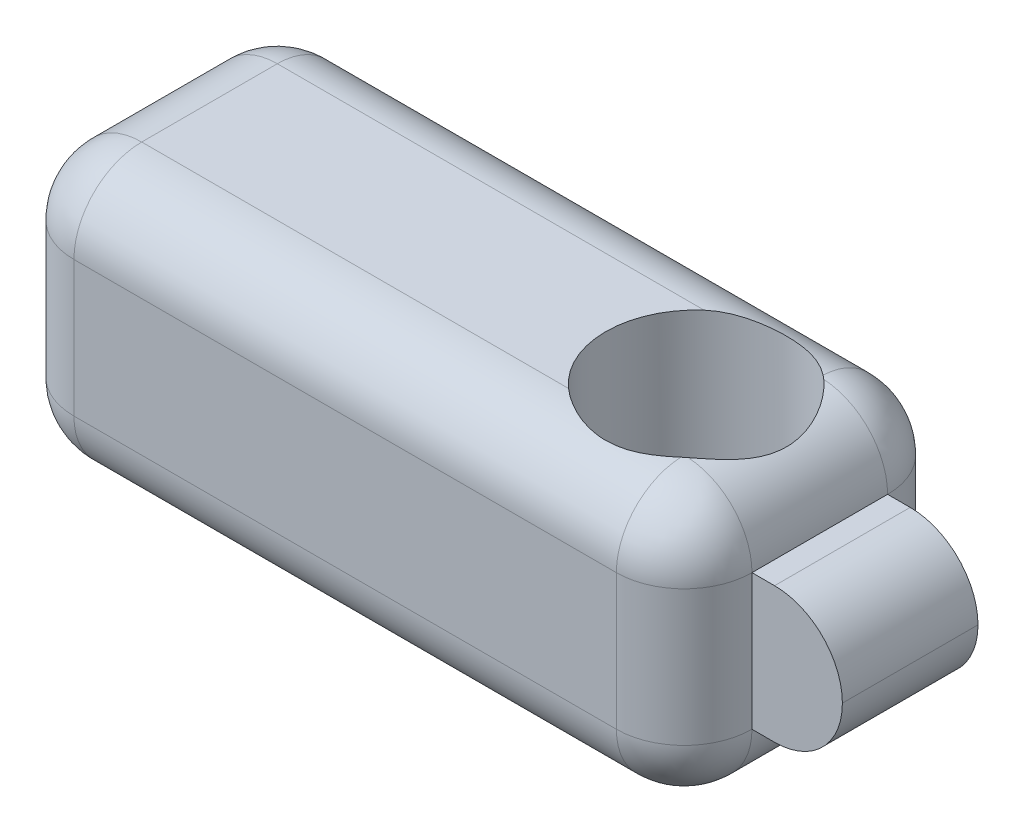
SolidWorks part; units mm, degrees
ref_plane "Front Plane" through (0, 0, 0) normal (0, 0, 1) x (1, 0, 0)
ref_plane "Top Plane" through (0, 0, 0) normal (0, 1, 0) x (1, 0, 0)
ref_plane "Right Plane" through (0, 0, 0) normal (1, 0, 0) x (0, 0, -1)
sketch "Sketch1" plane through (0, 0, 0) normal (0, 1, 0) x (1, 0, 0)
  line L1 (-75, 30) -> (75, 30)
  line L2 (-75, 30) -> (-75, -30)
  line L3 (-75, -30) -> (75, -30)
  line L4 (75, 30) -> (75, -30)
  line L5 (-75, 30) -> (75, -30) construction
  line L6 (-75, -30) -> (75, 30) construction
  point P0 (0, 0)
  dimension "D1" = 60
  dimension "D2" = 150
extrude "Boss-Extrude3" add sketch "Sketch1" along normal blind 60
sketch "Sketch3" plane through (-75, 0, 0) normal (-1, 0, 0) x (0, 0, 1)
  circle A0 centre (0, 30) radius 20
extrude "Cut-Extrude1" cut sketch "Sketch3" against normal blind 100
fillet "Fillet1" radius 15 12 edges at (75, 30, 30) (75, 60, 0) (75, 30, -30) (75, 0, 0) (-75, 0, 0) (-75, 30, 30) (-75, 60, 0) (-75, 30, -30) (0, 0, -30) (0, 0, 30) (0, 60, -30) (0, 60, 30)
sketch "Sketch5" plane through (0, 60, 0) normal (0, 1, 0) x (1, 0, 0)
  circle A0 centre (47.6462, 0) radius 20
extrude "Cut-Extrude2" cut sketch "Sketch5" against normal blind 40
sketch "Sketch6" plane through (75, 0, 0) normal (1, 0, 0) x (0, 0, -1)
  line L2 (-15, 45) -> (15, 45)
  line L3 (-15, 45) -> (-15, 15)
  line L4 (-15, 15) -> (15, 15)
  line L5 (15, 45) -> (15, 15)
  line L6 (-15, 45) -> (15, 15) construction
  line L7 (-15, 15) -> (15, 45) construction
  point P4 (0, 30)
extrude "Boss-Extrude4" add sketch "Sketch6" along normal blind 20
fillet "Fillet4" radius 15 1 edges at (95, 15, 0)
fillet "Fillet5" radius 15 3 edges at (95, 37.5, -15) (95, 45, 0) (95, 37.5, 15)
